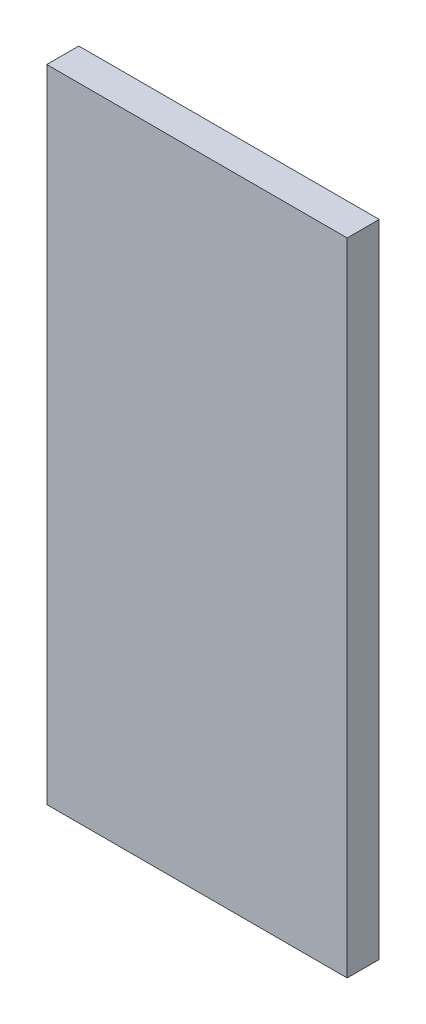
SolidWorks part; units mm, degrees
material "Простая углеродистая сталь"
ref_plane "Спереди" through (0, 0, 0) normal (0, 0, 1) x (1, 0, 0)
ref_plane "Сверху" through (0, 0, 0) normal (0, 1, 0) x (1, 0, 0)
ref_plane "Справа" through (0, 0, 0) normal (1, 0, 0) x (0, 0, -1)
sketch "Эскиз1" plane through (0, 0, 0) normal (0, 0, 1) x (1, 0, 0)
  line L1 (0, 0) -> (75, 0)
  line L2 (0, 0) -> (0, -160)
  line L3 (0, -160) -> (75, -160)
  line L4 (75, 0) -> (75, -160)
  dimension "D1" = 160
  dimension "D2" = 75
base flange "Базовая кромка1" sketch "Эскиз1" thickness 8 reverse thickness direction no parameters "D1"=3
sketch "Сгиб-Линии1" plane through (0, 0, 0) normal (0, 1, 0) x (1, 0, 0)
sketch "Граничная рамка1" plane through (0, 0, 0) normal (0, 1, 0) x (1, 0, 0)
sheet metal parameters "Листовой металл1" thickness 8 parameters "D1"=3
flat pattern "Развертка1" [suppressed]
sketch "Сгиб-Линии2" plane through (0, 0, 0) normal (0, 1, 0) x (1, 0, 0)
sketch "Граничная рамка2" [suppressed] plane through (0, 0, 0) normal (0, 1, 0) x (1, 0, 0)
